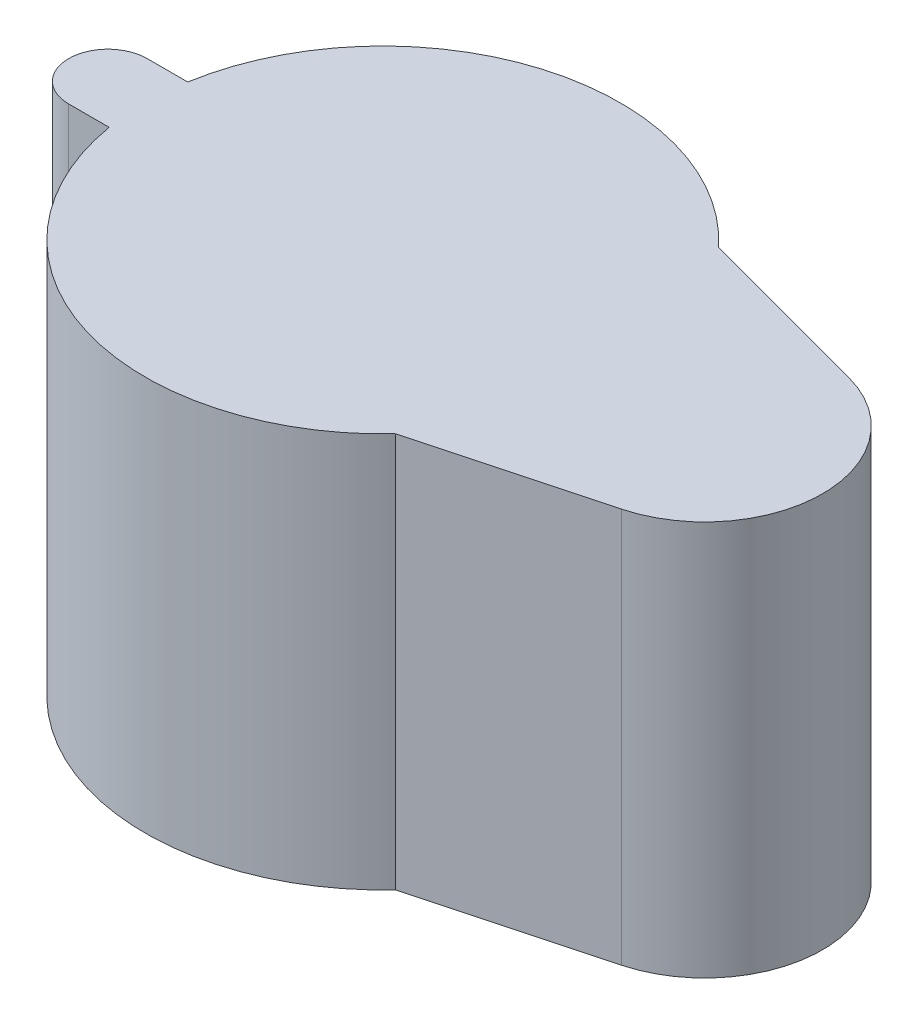
SolidWorks part; units mm, degrees
ref_plane "Front" through (0, 0, 0) normal (0, 0, 1) x (1, 0, 0)
ref_plane "Top" through (0, 0, 0) normal (0, 1, 0) x (1, 0, 0)
ref_plane "Right" through (0, 0, 0) normal (1, 0, 0) x (0, 0, -1)
ref_axis "X" through (-80.9, 0, 0) along (1, 0, 0)
ref_axis "Y" through (0, -50, 0) along (0, 1, 0)
ref_axis "Z" through (0, 0, -80.9) along (0, 0, 1)
sketch "Sketch1" plane through (0, 0, 0) normal (0, 1, 0) x (1, 0, 0)
  line L0 (-35, 5) -> (-29.8339, 5)
  line L1 (-35, -5) -> (-29.8339, -5)
  line L2 (44.8823, 14.4889) -> (22.1772, 20.5727)
  line L3 (44.8823, -14.4889) -> (22.1772, -20.5727)
  line L4 (41, 0) -> (0, 0) construction
  line L5 (0, 0) -> (-35, 0) construction
  arc A0 (-29.8339, -5) -> (22.1772, -20.5727) centre (0, 0) ccw
  arc A1 (-35, 5) -> (-35, -5) centre (-35, 0) ccw
  arc A2 (44.8823, -14.4889) -> (44.8823, 14.4889) centre (41, 0) ccw
  arc A3 (22.1772, 20.5727) -> (-29.8339, 5) centre (0, 0) ccw
  point P6 (-28.5051, 10.1252)
  point P13 (-34.8192, 0)
  point P14 (24.119, 18.2575)
  dimension "D1" = 60.5
  dimension "D2" = 15
  dimension "D3" = 5
  dimension "D4" = 96
  dimension "D5" = 35
  dimension "D6" = 30
extrude "Boss-Extrude1" add sketch "Sketch1" along normal blind 50.3
